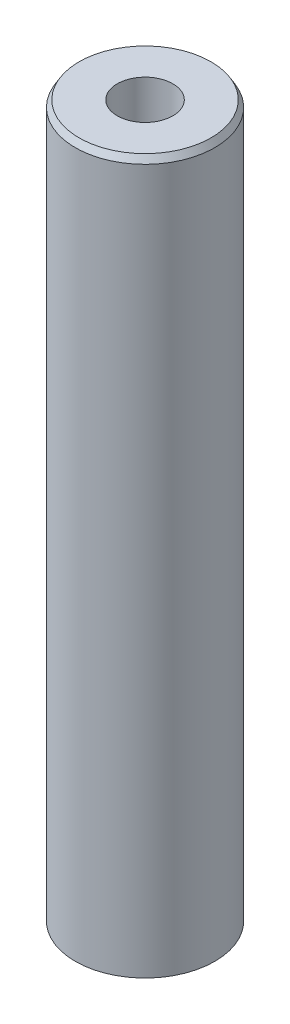
SolidWorks part; units mm, degrees
ref_plane "Front Plane" through (0, 0, 0) normal (0, 0, 1) x (1, 0, 0)
ref_plane "Top Plane" through (0, 0, 0) normal (0, 1, 0) x (1, 0, 0)
ref_plane "Right Plane" through (0, 0, 0) normal (1, 0, 0) x (0, 0, -1)
sketch "Sketch1" plane through (0, 0, 0) normal (0, 1, 0) x (1, 0, 0)
  circle A0 centre (0, 0) radius 35
  dimension "SHAFT_OD" = 70
extrude "Boss-Extrude1" add sketch "Sketch1" along normal blind 358.7562
sketch "Sketch2" plane through (0, 0, 0) normal (0, 1, 0) x (1, 0, 0)
  circle A0 centre (0, 0) radius 13.9433
  dimension "BORE_D" = 27.8865
extrude "Cut-Extrude1" cut sketch "Sketch2" along normal through all
chamfer "Chamfer1" distance 3.3 angle 30 2 edges at (0, 358.7562, 35) (0, 0, 35) first distance on face at (0, 358.7562, 35) first distance on face at (0, 0, 13.9433)
